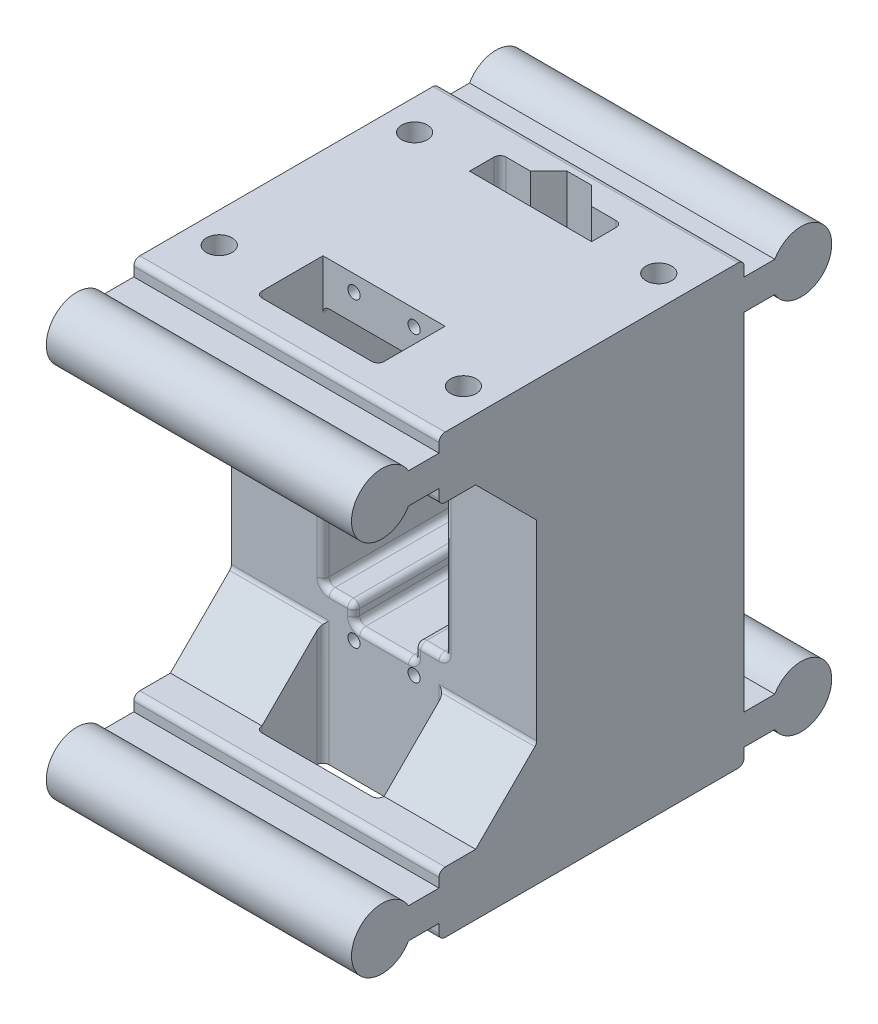
SolidWorks part; units mm, degrees
ref_plane "Plano frontal" through (0, 0, 0) normal (0, 0, 1) x (1, 0, 0)
ref_plane "Plano superior" through (0, 0, 0) normal (0, 1, 0) x (1, 0, 0)
ref_plane "Plano direito" through (0, 0, 0) normal (1, 0, 0) x (0, 0, -1)
sketch "Esboço2" plane through (0, 0, 0) normal (0, 0, 1) x (1, 0, 0)
  line L0 (0, 0) -> (0, 24.1482) construction
  line L1 (-10, 0) -> (10, 0) construction
  line L2 (10, 0) -> (10, -40)
  line L3 (10, 0) -> (-10, 0)
  line L4 (25, 0) -> (25, 7.05)
  line L5 (25, 7.05) -> (-25, 7.05)
  line L6 (0, 0) -> (0, 7.05) construction
  line L8 (25, -40) -> (25, 0)
  line L9 (-25, -40) -> (-25, 0)
  line L11 (-25, 0) -> (-25, 7.05)
  line L12 (-10, 0) -> (-10, -40)
  line L14 (-10, -40) -> (10, -40)
  line L15 (-25, -40) -> (-25, -64.65)
  line L16 (-25, -64.65) -> (25, -64.65)
  line L17 (25, -40) -> (25, -64.65)
  dimension "D1" = 20
  dimension "D2" = 7.05
  dimension "D3" = 40
  dimension "D4" = 15
  dimension "D5" = 24.65
  dimension "D6" = 50
extrude "Ressalto-extrusão2" add sketch "Esboço2" against normal blind 29
sketch "Esboço3" plane through (0, 0, 0) normal (0, 0, 1) x (1, 0, 0)
  line L0 (25, -64.65) -> (25, 7.05) construction
  line L1 (10, 7.05) -> (25, 7.05)
  line L2 (10, 7.05) -> (10, -2.95)
  line L3 (10, -2.95) -> (25, -2.95)
  line L4 (25, 7.05) -> (25, -2.95)
  line L5 (0, -15.95) -> (0, 15.95) construction
  line L6 (-25, 7.05) -> (-25, -2.95)
  line L7 (-10, -2.95) -> (-25, -2.95)
  line L8 (-10, 7.05) -> (-10, -2.95)
  line L9 (-10, 7.05) -> (-25, 7.05)
  line L11 (25, 7.05) -> (-25, 7.05) construction
  point P13 (0, 0)
  dimension "D1" = 10
extrude "Ressalto-extrusão3" add sketch "Esboço3" along normal blind 16
sketch "Esboço4" plane through (10, 0, 0) normal (-1, 0, 0) x (0, 0, 1)
  line L0 (16, -2.95) -> (0, -2.95) construction
  line L1 (16, 7.05) -> (11, 7.05)
  line L2 (16, 7.05) -> (16, -2.95)
  line L3 (16, -2.95) -> (11, -2.95)
  line L4 (11, 7.05) -> (11, -2.95)
  dimension "D1" = 5
extrude "Ressalto-extrusão4" add sketch "Esboço4" along normal up to surface (20 mm away) up to face at (-10, -8.975, -3.25)
sketch "Esboço5" plane through (0, 0, -29) normal (0, 0, -1) x (-1, 0, 0)
  line L1 (25, 7.05) -> (-25, 7.05)
  line L2 (25, 7.05) -> (25, -64.65)
  line L3 (25, -64.65) -> (-25, -64.65)
  line L4 (-25, 7.05) -> (-25, -64.65)
  point P8 (0, 0)
extrude "Ressalto-extrusão5" add sketch "Esboço5" along normal blind 5
sketch "Esboço6" plane through (-25, 0, 0) normal (-1, 0, 0) x (0, 0, 1)
  line L0 (16, 2.05) -> (25.3301, 2.05) construction
  line L1 (16, 7.05) -> (16, -2.95) construction
  line L2 (16, 4.55) -> (21, 4.55)
  line L3 (16, -0.45) -> (21, -0.45)
  line L4 (16, 7.05) -> (-34, 7.05) construction
  line L5 (16, -2.95) -> (0, -2.95) construction
  line L6 (16, 4.55) -> (16, -0.45)
  line L7 (16, 2.05) -> (-34, 2.05) construction
  line L8 (-34, -64.65) -> (-34, 7.05) construction
  line L9 (-9, 2.05) -> (-9, 7.05) construction
  line L10 (-34, 7.05) -> (16, 7.05) construction
  line L11 (-34, 2.05) -> (-43.3301, 2.05) construction
  line L12 (-34, 4.55) -> (-34, -0.45)
  line L13 (-34, -0.45) -> (-39, -0.45)
  line L14 (-34, 4.55) -> (-39, 4.55)
  arc A0 (21, -0.45) -> (21, 4.55) centre (25.3301, 2.05) ccw
  arc A1 (-39, -0.45) -> (-39, 4.55) centre (-43.3301, 2.05) cw
  dimension "D3" = 10
  dimension "D1" = 2.5
  dimension "D2" = 2.5
  dimension "D4" = 5
extrude "Ressalto-extrusão6" add sketch "Esboço6" against normal up to surface (50 mm away) up to face at (25, -20.1833, -6)
ref_plane "Plano1" through (0, -28.8, 0) normal (0, -1, 0) x (-1, 0, 0)
mirror "Espelhar2" about plane through (0, -28.8, 0) normal (0, -1, 0) of "Ressalto-extrusão4", "Ressalto-extrusão3", "Ressalto-extrusão6"
sketch "Esboço9" plane through (0, 0, 0) normal (0, 0, 1) x (1, 0, 0)
  line L0 (-10, -40) -> (10, -40) construction
  line L1 (-5, -37) -> (5, -37)
  line L2 (-5, -37) -> (-5, -43)
  line L3 (-5, -43) -> (5, -43)
  line L4 (5, -37) -> (5, -43)
  line L5 (-5, -37) -> (5, -43) construction
  line L6 (-5, -43) -> (5, -37) construction
  point P0 (0, -40)
  dimension "D1" = 10
  dimension "D2" = 6
extrude "Corte-extrusão1" cut sketch "Esboço9" against normal up to surface (29 mm away) up to face at (0, -20, -29)
sketch "Esboço10" plane through (0, 0, 0) normal (0, -1, 0) x (1, 0, 0)
  line L0 (10, -29) -> (10, 0) construction
  line L1 (-10, -29) -> (10, -29)
  line L2 (-10, -29) -> (-10, -24)
  line L3 (-10, -24) -> (10, -24)
  line L4 (10, -29) -> (10, -24)
  dimension "D1" = 5
extrude "Corte-extrusão2" cut sketch "Esboço10" against normal up to surface (7.05 mm away) up to face at (0, 7.05, 5.5)
sketch "Esboço11" plane through (0, 0, -29) normal (0, 0, 1) x (1, 0, 0)
  line L0 (0, 7.05) -> (0, -43) construction
  line L1 (-10, 7.05) -> (10, 7.05) construction
  line L2 (5, -43) -> (-5, -43) construction
  line L3 (0, -17.975) -> (10, -17.975) construction
  line L4 (10, -40) -> (10, 7.05) construction
  line L6 (-5, 7.05) -> (5, 7.05)
  line L7 (-5, 7.05) -> (-5, -43)
  line L8 (-5, -43) -> (5, -43)
  line L9 (5, 7.05) -> (5, -43)
  line L10 (-5, 7.05) -> (5, -43) construction
  line L11 (-5, -43) -> (5, 7.05) construction
extrude "Corte-extrusão3" cut sketch "Esboço11" against normal blind 3
chamfer "Chanfro4" distance 3 angle 45 2 edges at (-5, -17.975, -32) (5, -17.975, -32)
sketch "Esboço12" plane through (0, 0, 0) normal (0, 0, 1) x (1, 0, 0)
  line L0 (0, 7.05) -> (0, -54.65) construction
  line L1 (10, 7.05) -> (-10, 7.05) construction
  line L2 (25, -54.65) -> (-25, -54.65) construction
  line L4 (-4.925, 4.42) -> (4.925, 4.42) construction
  line L5 (-4.925, 4.42) -> (-4.925, -45) construction
  line L6 (-4.925, -45) -> (4.925, -45) construction
  line L7 (4.925, 4.42) -> (4.925, -45) construction
  circle A0 centre (-4.925, 4.42) radius 1
  circle A1 centre (4.925, 4.42) radius 1
  circle A2 centre (4.925, -45) radius 1
  circle A3 centre (-4.925, -45) radius 1
  point P10 (0, 4.42)
  dimension "D1" = 2
  dimension "D2" = 9.85
  dimension "D3" = 2.63
  dimension "D4" = 49.42
extrude "Corte-extrusão4" cut sketch "Esboço12" against normal blind 10
chamfer "Chanfro5" distance 10 angle 45 4 edges at (-17.5, -54.65, 0) (17.5, -54.65, 0) (17.5, -2.95, 0) (-17.5, -2.95, 0)
fillet "Filete2" radius 1 31 edges at (-10, 0, -12) (10, 0, -12) (-10, -40, -14.5) (10, -40, -14.5) (5, -40, -14.5) (5, -43, -14.5) (-5, -43, -14.5) (-5, -40, -14.5) (-5, -41.5, 0) (5, -41.5, 0) (7.5, -40, 0) (-7.5, -40, 0) (10, -59.65, 11) (-10, -59.65, 11) (10, -54.65, 0) (-10, -54.65, 0) (10, 2.05, 11) (-10, 2.05, 11) (0, -43, 0) (10, -26.475, 0) (-10, -26.475, 0) (10, -16.475, -29) (-10, -16.475, -29) (0, -64.65, -34) (0, 7.05, -34) (0, -64.65, 16) (0, -54.65, 16) (0, -2.95, 16) (0, 7.05, 16) (-17.5, -44.65, 0) (17.5, -44.65, 0)
sketch "Esboço16" plane through (0, 7.05, 0) normal (0, 1, 0) x (1, 0, 0)
  line L0 (0, 48.3301) -> (0, -30.3301) construction
  line L1 (25, 48.3301) -> (-25, 48.3301) construction
  line L2 (-25, -30.3301) -> (25, -30.3301) construction
  line L3 (25, 9) -> (-25, 9) construction
  line L4 (25, 33) -> (25, -15) construction
  line L5 (-25, 33) -> (-25, -15) construction
  line L6 (25, 33) -> (-25, 33) construction
  line L7 (-20, -7) -> (20, -7) construction
  line L8 (-20, -7) -> (-20, 25) construction
  line L9 (-20, 25) -> (20, 25) construction
  line L10 (20, -7) -> (20, 25) construction
  line L11 (-20, -7) -> (20, 25) construction
  line L12 (-20, 25) -> (20, -7) construction
  circle A0 centre (-20, -7) radius 2.1
  circle A1 centre (20, -7) radius 2.1
  circle A2 centre (20, 25) radius 2.1
  circle A3 centre (-20, 25) radius 2.1
  point P12 (0, 9)
  dimension "D1" = 4.2
  dimension "D2" = 5
  dimension "D3" = 8
extrude "Corte-extrusão5" cut sketch "Esboço16" against normal blind 15 and the other way through all
